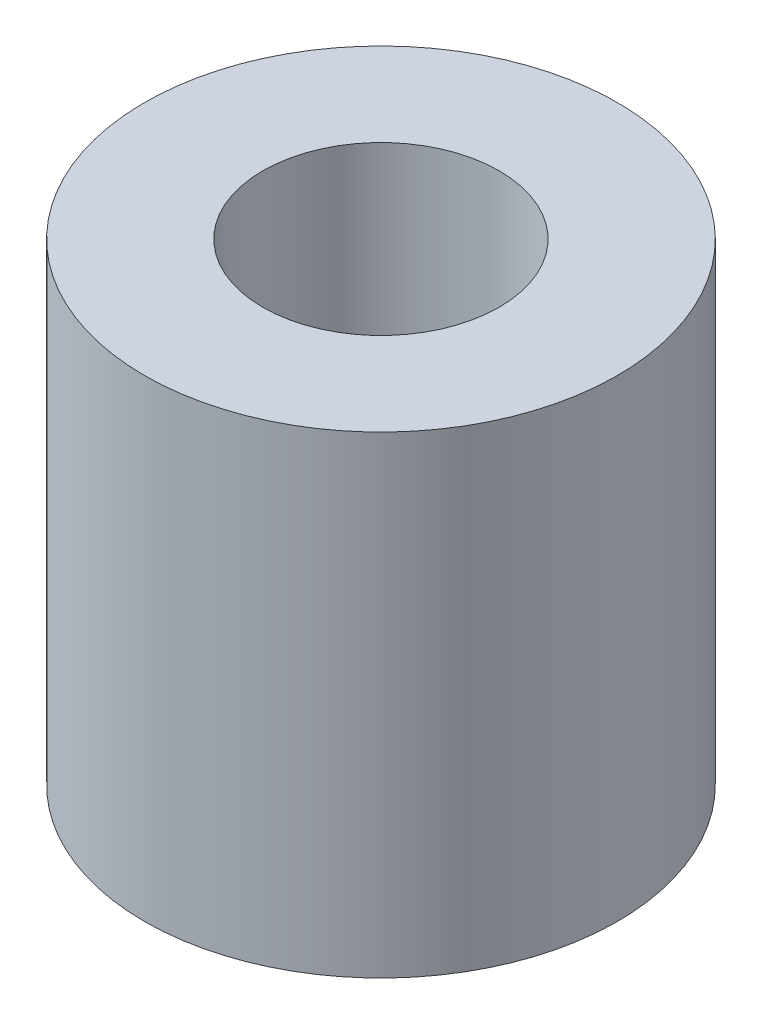
SolidWorks part; units mm, degrees
material "Bambu PAHT-CF"
ref_plane "Front Plane" through (0, 0, 0) normal (0, 0, 1) x (1, 0, 0)
ref_plane "Top Plane" through (0, 0, 0) normal (0, 1, 0) x (1, 0, 0)
ref_plane "Right Plane" through (0, 0, 0) normal (1, 0, 0) x (0, 0, -1)
sketch "Sketch2" plane through (0, 0, 0) normal (0, 1, 0) x (1, 0, 0)
  circle A0 centre (0, 0) radius 8.75
  circle A1 centre (0, 0) radius 17.5
  dimension "D1" = 17.5
  dimension "D2" = 35
extrude "Boss-Extrude1" add sketch "Sketch2" along normal blind 35
